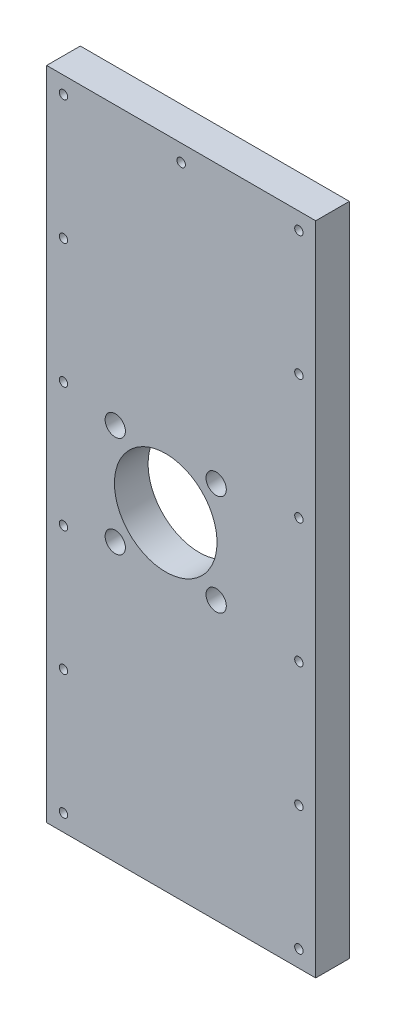
SolidWorks part; units mm, degrees
ref_plane "Ebene vorne" through (0, 0, 0) normal (0, 0, 1) x (1, 0, 0)
ref_plane "Ebene oben" through (0, 0, 0) normal (0, 1, 0) x (1, 0, 0)
ref_plane "Ebene rechts" through (0, 0, 0) normal (1, 0, 0) x (0, 0, -1)
sketch "Skizze1" plane through (0, 0, 0) normal (0, 0, 1) x (1, 0, 0)
  line L1 (-69.0594, 70.0995) -> (10.9406, 70.0995)
  line L2 (-69.0594, 70.0995) -> (-69.0594, -124.9005)
  line L3 (-69.0594, -124.9005) -> (10.9406, -124.9005)
  line L4 (10.9406, 70.0995) -> (10.9406, -124.9005)
  dimension "D1" = 195
  dimension "D2" = 80
extrude "Aufsatz-Linear austragen1" add sketch "Skizze1" against normal blind 10
sketch "Skizze2" plane through (0, 0, -10) normal (0, 0, -1) x (-1, 0, 0)
  line L0 (33.6594, 70.0995) -> (33.6594, -124.9005) construction
  line L1 (-10.9406, 70.0995) -> (69.0594, 70.0995) construction
  line L2 (69.0594, -124.9005) -> (-10.9406, -124.9005) construction
  line L3 (33.6594, -27.4005) -> (69.0594, -27.4005) construction
  line L4 (69.0594, 70.0995) -> (69.0594, -124.9005) construction
  line L5 (18.6594, -12.4005) -> (48.6594, -12.4005) construction
  line L6 (48.6594, -12.4005) -> (48.6594, -42.4005) construction
  line L7 (48.6594, -42.4005) -> (18.6594, -42.4005) construction
  line L8 (18.6594, -42.4005) -> (18.6594, -12.4005) construction
  line L9 (18.6594, -12.4005) -> (48.6594, -42.4005) construction
  circle A0 centre (18.6594, -12.4005) radius 3.015
  circle A1 centre (48.6594, -12.4005) radius 3.015
  circle A2 centre (18.6594, -42.4005) radius 3.015
  circle A3 centre (48.6594, -42.4005) radius 3.015
  circle A4 centre (33.6594, -27.4005) radius 15.25
  point P22 (33.6594, -27.4005)
  dimension "D1" = 30
  dimension "D3" = 6.03
  dimension "D2" = 30
  dimension "D4" = 35.4
extrude "Schnitt-Linear austragen1" cut sketch "Skizze2" against normal blind 10
sketch "Skizze3" plane through (0, 0, -10) normal (0, 0, -1) x (-1, 0, 0)
  line L0 (-5.9406, 65.0995) -> (64.0594, 65.0995) construction
  line L1 (29.0594, 65.0995) -> (29.0594, 70.0995) construction
  line L2 (-10.9406, 70.0995) -> (69.0594, 70.0995) construction
  line L3 (69.0594, 70.0995) -> (69.0594, -124.9005) construction
  line L4 (-5.9406, -119.9005) -> (64.0594, -119.9005) construction
  line L5 (29.0594, -119.9005) -> (29.0594, -124.9005) construction
  line L6 (69.0594, -124.9005) -> (-10.9406, -124.9005) construction
  line L7 (-5.9406, 28.0995) -> (-5.9406, -8.9005) construction
  line L8 (-5.9406, -8.9005) -> (-5.9406, -45.9005) construction
  line L9 (-5.9406, -45.9005) -> (-5.9406, -82.9005) construction
  line L10 (64.0594, -119.9005) -> (64.0594, -82.9005) construction
  line L11 (64.0594, -82.9005) -> (64.0594, -45.9005) construction
  line L12 (64.0594, -45.9005) -> (64.0594, -8.9005) construction
  line L13 (-5.9406, 28.0995) -> (-5.9406, 65.0995) construction
  line L14 (-5.9406, -119.9005) -> (-5.9406, -82.9005) construction
  line L15 (64.0594, -8.9005) -> (64.0594, 28.0995) construction
  line L16 (64.0594, 28.0995) -> (64.0594, 65.0995) construction
  circle A0 centre (29.0594, 65.0995) radius 2.5
  circle A1 centre (-5.9406, 65.0995) radius 2.5
  circle A2 centre (64.0594, 65.0995) radius 2.5
  circle A3 centre (29.0594, -119.9005) radius 2.5
  circle A4 centre (-5.9406, -119.9005) radius 2.5
  circle A5 centre (64.0594, -119.9005) radius 2.5
  circle A6 centre (-5.9406, 28.0995) radius 2.5
  circle A7 centre (-5.9406, -8.9005) radius 2.5
  circle A8 centre (-5.9406, -45.9005) radius 2.5
  circle A9 centre (-5.9406, -82.9005) radius 2.5
  circle A10 centre (64.0594, -82.9005) radius 2.5
  circle A11 centre (64.0594, -45.9005) radius 2.5
  circle A12 centre (64.0594, -8.9005) radius 2.5
  circle A13 centre (64.0594, 28.0995) radius 2.5
  dimension "D3" = 5
  dimension "D1" = 5
  dimension "D2" = 5
extrude "Schnitt-Linear austragen2" cut sketch "Skizze3" against normal blind 5
sketch "Skizze6" plane through (0, 0, 0) normal (0, 0, 1) x (1, 0, 0)
  line L0 (-64.0594, 65.0995) -> (-64.0594, 28.0995) construction
  line L1 (-64.0594, 28.0995) -> (-64.0594, -8.9005) construction
  line L2 (-64.0594, -8.9005) -> (-64.0594, -45.9005) construction
  line L3 (-64.0594, -45.9005) -> (-64.0594, -82.9005) construction
  line L4 (-64.0594, -82.9005) -> (-64.0594, -119.9005) construction
  line L5 (-64.0594, 65.0995) -> (5.9406, 65.0995) construction
  line L6 (5.9406, -119.9005) -> (5.9406, -82.9005) construction
  line L7 (5.9406, -82.9005) -> (5.9406, -45.9005) construction
  line L8 (5.9406, -45.9005) -> (5.9406, -8.9005) construction
  line L9 (5.9406, -8.9005) -> (5.9406, 28.0995) construction
  line L10 (5.9406, 28.0995) -> (5.9406, 65.0995) construction
  line L11 (-64.0594, -119.9005) -> (5.9406, -119.9005) construction
  line L12 (10.9406, 70.0995) -> (-69.0594, 70.0995) construction
  line L14 (-29.0594, 65.0995) -> (-29.0594, 70.0995) construction
  line L15 (-69.0594, -124.9005) -> (10.9406, -124.9005) construction
  circle A0 centre (-64.0594, 65.0995) radius 1.25
  circle A1 centre (-29.0594, 65.0995) radius 1.25
  circle A2 centre (5.9406, 65.0995) radius 1.25
  circle A3 centre (-64.0594, 28.0995) radius 1.25
  circle A4 centre (-64.0594, -8.9005) radius 1.25
  circle A5 centre (-64.0594, -45.9005) radius 1.25
  circle A6 centre (-64.0594, -82.9005) radius 1.25
  circle A7 centre (-64.0594, -119.9005) radius 1.25
  circle A8 centre (5.9406, -119.9005) radius 1.25
  circle A9 centre (5.9406, -82.9005) radius 1.25
  circle A10 centre (5.9406, -45.9005) radius 1.25
  circle A11 centre (5.9406, -8.9005) radius 1.25
  circle A12 centre (5.9406, 28.0995) radius 1.25
  dimension "D2" = 2.5
  dimension "D1" = 5
  dimension "D3" = 5
extrude "Schnitt-Linear austragen4" cut sketch "Skizze6" against normal blind 5
